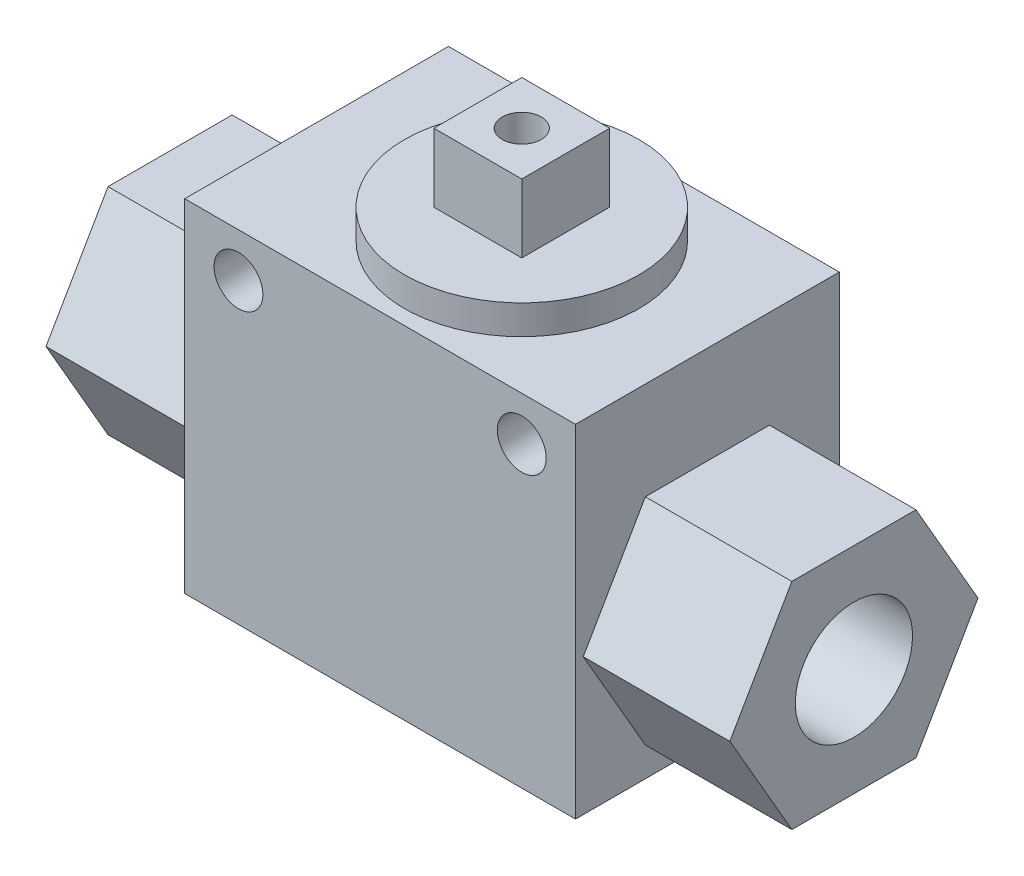
SolidWorks part; units mm, degrees
ref_plane "Front Plane" through (0, 0, 0) normal (0, 0, 1) x (1, 0, 0)
ref_plane "Top Plane" through (0, 0, 0) normal (0, 1, 0) x (1, 0, 0)
ref_plane "Right Plane" through (0, 0, 0) normal (1, 0, 0) x (0, 0, -1)
sketch "Szkic1" plane through (0, 0, 0) normal (0, 0, 1) x (1, 0, 0)
  line L0 (0, 35) -> (0, 33)
  line L1 (0, 0) -> (40, 0)
  line L2 (0, 0) -> (0, 35)
  line L3 (0, 35) -> (40, 35)
  line L4 (40, 0) -> (40, 35)
  line L5 (0, 33) -> (5.5, 33)
  line L6 (5.5, 33) -> (5.5, 30.5)
  line L7 (40, 35) -> (40, 33)
  line L8 (40, 33) -> (34.5, 33)
  line L9 (34.5, 33) -> (34.5, 30.5)
  circle A0 centre (5.5, 30.5) radius 2.5
  circle A1 centre (34.5, 30.5) radius 2.5
  dimension "D1" = 35
  dimension "D2" = 40
  dimension "D3" = 2
  dimension "D4" = 5.5
  dimension "D5" = 2.5
  dimension "D6" = 5.5
extrude "Dodanie-wyciągnięcie1" add sketch "Szkic1" along normal blind 13.5 and the other way blind 13.5 contours A1 L4 L3 L0 A0 L2 L1 region at (20, 17.1248, 0)
sketch "Szkic2" plane through (40, 0, 0) normal (1, 0, 0) x (0, 0, -1)
  line L0 (0, 0) -> (0, 14)
  line L2 (-12.7017, 14) -> (-6.3509, 3)
  line L3 (-6.3509, 3) -> (6.3509, 3)
  line L4 (6.3509, 3) -> (12.7017, 14)
  line L5 (12.7017, 14) -> (6.3509, 25)
  line L6 (6.3509, 25) -> (-6.3509, 25)
  line L7 (-6.3509, 25) -> (-12.7017, 14)
  circle A0 centre (0, 14) radius 3
  circle A1 centre (0, 14) radius 6
  circle A2 centre (0, 14) radius 11
  circle A3 centre (0, 14) radius 11 construction
  dimension "D2" = 22
  dimension "D3" = 12
  dimension "D4" = 6
  dimension "D1" = 14
  dimension "D5" = 11
extrude "Dodanie-wyciągnięcie2" add sketch "Szkic2" along normal blind 15 contours A2 L6 L7 | A2 L7 L2 | A2 A1 | A2 L2 L3 | A2 L3 L4 | A2 L4 L5 | A2 L5 L6 region at (40, 4.154, -5.6846) region at (40, 4.154, 5.6846) region at (40, 4.7432, 5.3444) region at (40, 14, 11.3692) region at (40, 14, -11.3692) region at (40, 23.846, 5.6846) region at (40, 23.846, -5.6846)
extrude "Wytnij-wyciągnięcie2" cut sketch "Szkic2<4>" against normal blind 40 contours A0 region at (40, 16.0613, 2.0613)
sketch "Szkic2<4>" plane through (40, 0, 0) normal (1, 0, 0) x (0, 0, -1) same geometry as "Szkic2"
extrude "Dodanie-wyciągnięcie3" add sketch "Szkic2<6>" against normal blind 15 from offset 40 contours A2 L6 L7 | A2 L7 L2 | A2 L2 L3 | A2 L3 L4 | A2 L4 L5 | A2 L5 L6 | A2 A1 region at (40, 4.154, -5.6846) region at (40, 4.154, 5.6846) region at (40, 4.7432, 5.3444) region at (40, 14, 11.3692) region at (40, 14, -11.3692) region at (40, 23.846, 5.6846) region at (40, 23.846, -5.6846) offset against normal yes
sketch "Szkic2<6>" plane through (40, 0, 0) normal (1, 0, 0) x (0, 0, -1) same geometry as "Szkic2"
sketch "Szkic3" plane through (0, 0, 0) normal (0, 1, 0) x (1, 0, 0)
  line L0 (0, 0) -> (21, 0)
  line L1 (21, 0) -> (16.5, 0)
  line L2 (16.5, 0) -> (25.5, 0)
  line L3 (16.5, 0) -> (16.5, 4.5)
  line L5 (16.5, 4.5) -> (25.5, 4.5)
  line L6 (16.5, 4.5) -> (16.5, -4.5)
  line L7 (16.5, -4.5) -> (25.5, -4.5)
  line L8 (25.5, 4.5) -> (25.5, -4.5)
  circle A0 centre (21, 0) radius 12
  circle A1 centre (21, 0) radius 2
  dimension "D2" = 24
  dimension "D8" = 4
  dimension "D1" = 21
  dimension "D3" = 4.5
  dimension "D4" = 4.5
  dimension "D5" = 4.5
  dimension "D6" = 9
  dimension "D7" = 9
extrude "Dodanie-wyciągnięcie4" add sketch "Szkic3" along normal blind 3 from offset 35 contours A0 L3 L5 L8 L7 L6 region at (21, 0, -11.6606)
extrude "Dodanie-wyciągnięcie5" add sketch "Szkic3<3>" along normal blind 10 from offset 35 contours L8 L5 L3 L0 L2 | L8 L2 L0 L6 L7 region at (21, 0, -2.5073) region at (21, 0, 2.5073)
sketch "Szkic3<3>" plane through (0, 0, 0) normal (0, 1, 0) x (1, 0, 0) same geometry as "Szkic3"
